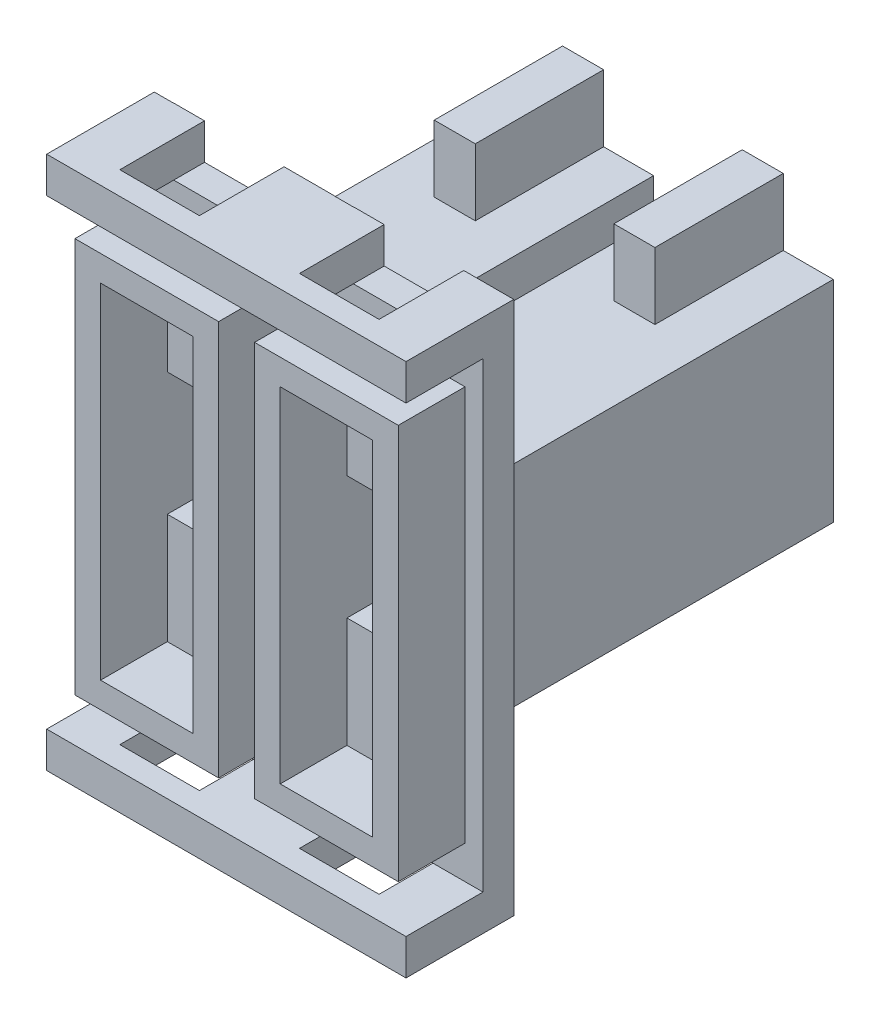
SolidWorks part; units mm, degrees
ref_plane "Спереди" through (0, 0, 0) normal (0, 0, 1) x (1, 0, 0)
ref_plane "Сверху" through (0, 0, 0) normal (0, 1, 0) x (1, 0, 0)
ref_plane "Справа" through (0, 0, 0) normal (1, 0, 0) x (0, 0, -1)
ref_plane "Плоскость1" through (0, 0, 1.05) normal (0, 0, 1) x (1, 0, 0)
sketch "Эскиз1" plane through (0, 0, 1.05) normal (0, 0, 1) x (1, 0, 0)
  line L0 (0, 5.2) -> (-3.125, 5.2)
  line L1 (-3.125, 5.2) -> (-3.125, -5.2)
  line L2 (-3.125, -5.2) -> (0, -5.2)
  line L3 (0, -5.2) -> (0, 5.2)
  dimension "D1" = 3.125
  dimension "D2" = 10.4
extrude "Бобышка-Вытянуть1" add sketch "Эскиз1" against normal blind 2.1
ref_plane "Плоскость2" through (0, 0, -0.45) normal (0, 0, -1) x (-1, 0, 0)
sketch "Эскиз2" plane through (0, 0, -0.45) normal (0, 0, -1) x (-1, 0, 0)
  line L0 (3.125, 4.5) -> (-3.125, 4.5)
  line L1 (-3.125, 4.5) -> (-3.125, -4.5)
  line L2 (-3.125, -4.5) -> (3.125, -4.5)
  line L3 (3.125, -4.5) -> (3.125, 4.5)
extrude "Вырез-Вытянуть1" cut sketch "Эскиз2" against normal up to next
sketch "Эскиз3" plane through (0, 0, -0.45) normal (0, 0, -1) x (-1, 0, 0)
  line L0 (0.975, 4.5) -> (2.525, 4.5)
  line L1 (2.525, 4.5) -> (2.525, 5.2)
  line L2 (2.525, 5.2) -> (0.975, 5.2)
  line L3 (0.975, 5.2) -> (0.975, 4.5)
extrude "Вырез-Вытянуть2" cut sketch "Эскиз3" against normal blind 1.05
sketch "Эскиз5" plane through (0, 0, -0.45) normal (0, 0, -1) x (-1, 0, 0)
  line L0 (0.975, -5.2) -> (2.525, -5.2)
  line L1 (2.525, -5.2) -> (2.525, -4.5)
  line L2 (2.525, -4.5) -> (0.975, -4.5)
  line L3 (0.975, -4.5) -> (0.975, -5.2)
extrude "Вырез-Вытянуть4" cut sketch "Эскиз5" against normal blind 1.05
ref_plane "Плоскость3" through (0, 0, -7.65) normal (0, 0, -1) x (-1, 0, 0)
sketch "Эскиз8" plane through (0, 0, -7.65) normal (0, 0, -1) x (-1, 0, 0)
  line L0 (3.125, 2.05) -> (0.375, 2.05)
  line L1 (0.375, 2.05) -> (0.375, -2.05)
  line L2 (3.125, -2.05) -> (3.125, 2.05)
  arc A0 (0.375, -2.05) -> (3.125, -2.05) centre (1.75, -3.5024) cw
extrude "Бобышка-Вытянуть3" add sketch "Эскиз8" against normal up to surface (6.6 mm away) up to face at (-1.5625, 0, -1.05)
ref_plane "Плоскость4" through (0, 0, 0.85) normal (0, 0, 1) x (1, 0, 0)
sketch "Эскиз9" plane through (0, 0, 0.85) normal (0, 0, 1) x (1, 0, 0)
  line L0 (-0.35, -3.85) -> (-0.35, 3.85)
  line L1 (-0.35, 3.85) -> (-3.15, 3.85)
  line L2 (-3.15, 3.85) -> (-3.15, -3.85)
  line L3 (-3.15, -3.85) -> (-0.35, -3.85)
extrude "Бобышка-Вытянуть4" add sketch "Эскиз9" against normal up to surface (1.3 mm away) up to face at (-1.6875, 0, -0.45)
sketch "Эскиз11" plane through (0, 0, -0.45) normal (0, 0, -1) x (-1, 0, 0)
  line L0 (0.85, 3.35) -> (0.85, -3.35)
  line L1 (0.85, -3.35) -> (2.65, -3.35)
  line L2 (2.65, -3.35) -> (2.65, 3.35)
  line L3 (2.65, 3.35) -> (0.85, 3.35)
extrude "Вырез-Вытянуть6" cut sketch "Эскиз11" against normal up to next
ref_plane "Плоскость5" through (0, 0, -5.65) normal (0, 0, -1) x (-1, 0, 0)
sketch "Эскиз14" plane through (0, 0, -5.65) normal (0, 0, -1) x (-1, 0, 0)
  line L0 (0.85, -1.2) -> (2.65, -1.2)
  line L1 (2.65, -1.2) -> (2.65, 1.2)
  line L2 (2.65, 1.2) -> (0.85, 1.2)
  line L3 (0.85, 1.2) -> (0.85, -1.2)
extrude "Вырез-Вытянуть9" cut sketch "Эскиз14" against normal up to next
ref_plane "Плоскость6" through (0, -4.5, 0) normal (0, 1, 0) x (1, 0, 0)
sketch "Эскиз16" plane through (0, -4.5, 0) normal (0, 1, 0) x (1, 0, 0)
  line L0 (-0.975, 1.05) -> (-2.525, 1.05)
  line L1 (-2.525, 1.05) -> (-2.525, 0.45)
  line L2 (-2.525, 0.45) -> (-0.975, 0.45)
  line L3 (-0.975, 0.45) -> (-0.975, 1.05)
extrude "Вырез-Вытянуть11" cut sketch "Эскиз16" against normal up to next
ref_plane "Плоскость7" through (0, 4.5, 0) normal (0, -1, 0) x (1, 0, 0)
sketch "Эскиз17" plane through (0, 4.5, 0) normal (0, -1, 0) x (1, 0, 0)
  line L0 (-2.525, -1.05) -> (-0.975, -1.05)
  line L1 (-0.975, -1.05) -> (-0.975, -0.45)
  line L2 (-0.975, -0.45) -> (-2.525, -0.45)
  line L3 (-2.525, -0.45) -> (-2.525, -1.05)
extrude "Вырез-Вытянуть12" cut sketch "Эскиз17" against normal up to next
ref_plane "Плоскость8" through (-3.5, 0, 0) normal (-1, 0, 0) x (0, -1, 0)
sketch "Эскиз19" plane through (-3.5, 0, 0) normal (-1, 0, 0) x (0, -1, 0)
  line L2 (1.65, -1.0464) -> (5.2, -1.0464)
  line L3 (5.2, -1.0464) -> (5.2, 1.05)
  line L4 (5.2, 1.05) -> (4.5, 1.05)
  line L5 (4.5, 1.05) -> (4.5, -0.45)
  line L6 (4.5, -0.45) -> (-4.5, -0.45)
  line L7 (-4.5, -0.45) -> (-4.5, 1.05)
  line L8 (-4.5, 1.05) -> (-5.2, 1.05)
  line L9 (-5.2, 1.05) -> (-5.2, -1.0464)
  line L10 (-5.2, -1.0464) -> (1.65, -1.0464)
extrude "Бобышка-Вытянуть6" add sketch "Эскиз19" against normal up to surface (0.375 mm away) up to face at (-3.125, 0.225, -0.75)
ref_plane "Плоскость9" through (3.5, 0, 0) normal (1, 0, 0) x (0, 0, -1)
ref_plane "Плоскость10" through (0, 3.35, 0) normal (0, 1, 0) x (1, 0, 0)
sketch "Эскиз21" plane through (0, 3.35, 0) normal (0, 1, 0) x (1, 0, 0)
  line L0 (-2.15, 7.65) -> (-2.15, 5.15)
  line L1 (-2.15, 5.15) -> (-1.35, 5.15)
  line L2 (-1.35, 5.15) -> (-1.35, 7.65)
  line L3 (-1.35, 7.65) -> (-2.15, 7.65)
extrude "Бобышка-Вытянуть8" add sketch "Эскиз21" against normal up to surface (1.3 mm away) up to face at (-2.0937, 2.05, -3.525)
hole_wizard "Диаметр отверстия Ø2.1 (2.1)2" positions "Эскиз26" profile "Эскиз25" hole size "Ø2.1" standard "Ansi Metric"
sketch "Эскиз26" plane through (0, 0, -7.65) normal (0, 0, -1) x (-1, 0, 0)
  point P0 (1.75, 0)
sketch "Эскиз25" plane through (-1.75, 0, -7.65) normal (1, 0, 0) x (0, 1, 0)
  line L0 (0, 0) -> (0, 1.2)
  line L1 (0, 1.2) -> (1.05, 1.2)
  line L2 (1.05, 1.2) -> (1.05, 0)
  line L5 (1.05, 0) -> (0, 0)
  line L10 (0, 1.2) -> (-1.05, 1.2) construction
  line L11 (0, -6.35) -> (0, 107.95) construction
  dimension "Диаметр отверстия" = 2.1
  dimension "Глубина отверстия" = 1.2
  dimension "Угол заточки сверла" = 180
hole_wizard "Диаметр отверстия Ø1.5 (1.5)1" positions "Эскиз28" profile "Эскиз27" hole size "Ø1.5" standard "Ansi Metric"
sketch "Эскиз28" plane through (0, 0, -5.65) normal (0, 0, 1) x (1, 0, 0)
  point P0 (-1.75, 0)
sketch "Эскиз27" plane through (-1.75, 0, -5.65) normal (1, 0, 0) x (0, -1, 0)
  line L0 (0, 0) -> (0, 2)
  line L1 (0, 2) -> (0.75, 2)
  line L2 (0.75, 2) -> (0.75, 0)
  line L5 (0.75, 0) -> (0, 0)
  line L11 (0, -6.35) -> (0, 107.95) construction
  dimension "Диаметр сквозного отверстия" = 1.5
  dimension "Глубина сквозного отверстия" = 2
fillet "Скругление1" radius 0.3 1 edges at (-2.8, 0, -6.45) tangent propagation no
pattern_linear "Линейный массив1" count 2 spacing 3.5 along (1, 0, 0) of "Бобышка-Вытянуть1", "Вырез-Вытянуть1", "Вырез-Вытянуть2", "Вырез-Вытянуть4", "Бобышка-Вытянуть3", "Бобышка-Вытянуть4", "Вырез-Вытянуть6", "Вырез-Вытянуть9", "Вырез-Вытянуть11", "Вырез-Вытянуть12", "Бобышка-Вытянуть6", "Бобышка-Вытянуть8", "Диаметр отверстия Ø2.1 (2.1)2", "Диаметр отверстия Ø1.5 (1.5)1", "Скругление1"
